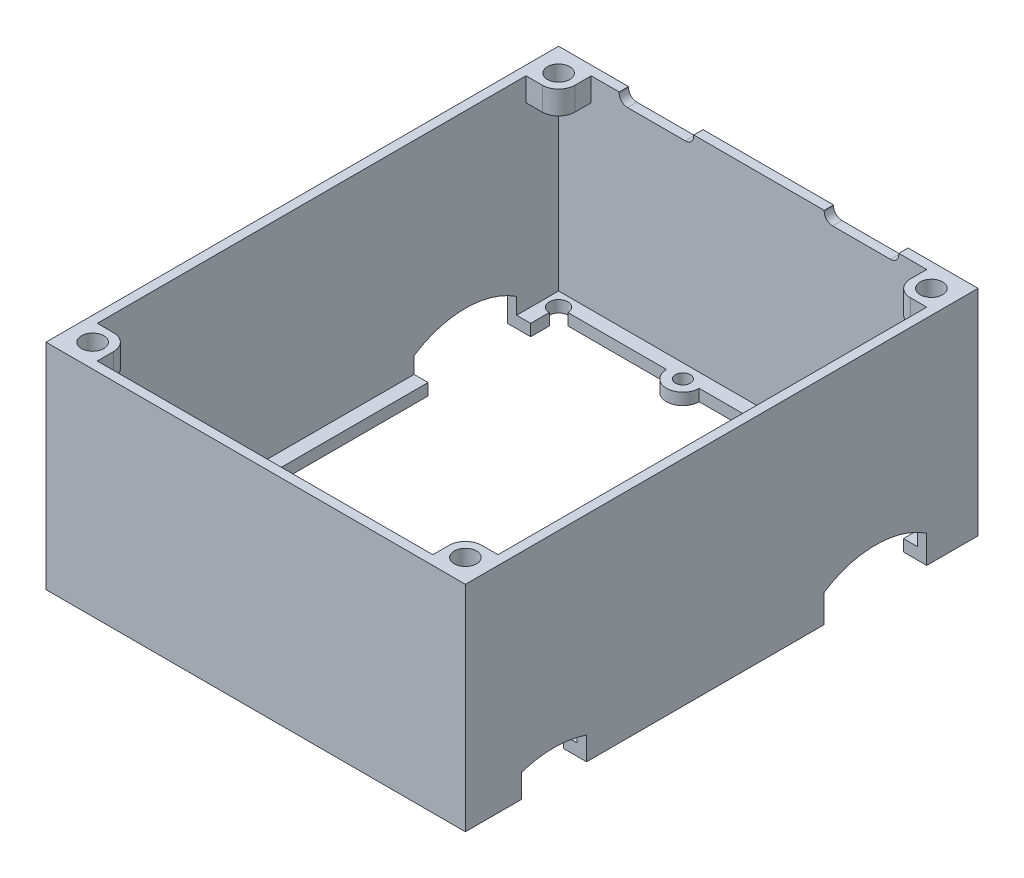
SolidWorks part; units mm, degrees
other "Markup1"
sketch "Sketch7" plane through (-45, 41, -55) normal (0, 1, 0) x (1, 0, 0)
other "DetailItem1"
ref_plane "Front Plane" through (0, 0, 0) normal (0, 0, 1) x (1, 0, 0)
ref_plane "Top Plane" through (0, 0, 0) normal (0, 1, 0) x (1, 0, 0)
ref_plane "Right Plane" through (0, 0, 0) normal (1, 0, 0) x (0, 0, -1)
sketch "Sketch1" plane through (0, 0, 0) normal (0, 1, 0) x (1, 0, 0)
  line L1 (-45, -55) -> (45, -55)
  line L2 (-45, -55) -> (-45, 55)
  line L3 (-45, 55) -> (45, 55)
  line L4 (45, -55) -> (45, 55)
  line L5 (-45, -55) -> (45, 55) construction
  line L6 (-45, 55) -> (45, -55) construction
  point P0 (0, 0)
  dimension "D1" = 90
  dimension "D2" = 110
extrude "Boss-Extrude1" add sketch "Sketch1" along normal blind 2.5
sketch "Sketch2" plane through (0, 2.5, 0) normal (0, 1, 0) x (1, 0, 0)
  line L11 (45, 55) -> (-45, 55) construction
  line L12 (-40, 50) -> (-16.8333, 50)
  line L13 (-40, 50) -> (-40, -50)
  line L14 (-40, -50) -> (-21.5208, -50)
  line L15 (40, 50) -> (40, -50)
  line L16 (-40, 50) -> (40, -50) construction
  line L17 (-40, -50) -> (40, 50) construction
  line L18 (45, -55) -> (45, 55) construction
  line L19 (30.5, 50) -> (40, 50)
  line L20 (-9.8333, 50) -> (23.5, 50)
  line L21 (-14.8126, -50) -> (18.9792, -50)
  line L22 (25.6874, -50) -> (40, -50)
  arc A0 (23.5, 50) -> (30.5, 50) centre (27, 50) ccw
  arc A1 (-14.8126, -50) -> (-21.5208, -50) centre (-18.1667, -51) ccw
  arc A2 (-16.8333, 50) -> (-9.8333, 50) centre (-13.3333, 50) ccw
  arc A3 (25.6874, -50) -> (18.9792, -50) centre (22.3333, -51) ccw
  point P0 (0, 0)
  dimension "D4" = 7
  dimension "D6" = 7
  dimension "D1" = 5
  dimension "D2" = 5
  dimension "D3" = 27
  dimension "D5" = 13.3333
  dimension "D7" = 22.3333
  dimension "D8" = 18.1667
  dimension "D9" = 51
extrude "Cut-Extrude1" cut sketch "Sketch2" against normal through all
sketch "Sketch6" plane through (0, 2.5, 0) normal (0, 1, 0) x (1, 0, 0)
  circle A0 centre (-13.3333, 50) radius 1.6
  circle A1 centre (27, 50) radius 1.6
  circle A2 centre (22.3333, -51) radius 1.6
  circle A3 centre (-18.1667, -51) radius 1.6
  dimension "D1" = 3.2
extrude "Cut-Extrude4" cut sketch "Sketch6" against normal through all
sketch "Sketch3" plane through (0, 2.5, 0) normal (0, 1, 0) x (1, 0, 0)
  line L0 (45, 55) -> (-45, 55) construction
  line L1 (43, -53) -> (-43, -53)
  line L2 (43, -53) -> (43, 53)
  line L3 (43, 53) -> (-43, 53)
  line L4 (-43, -53) -> (-43, 53)
  line L5 (43, -53) -> (-43, 53) construction
  line L6 (43, 53) -> (-43, -53) construction
  line L7 (-45, 55) -> (-45, -55) construction
  point P0 (0, 0)
  line M16 (45, -55) -> (45, 55)
  line M17 (45, 55) -> (-45, 55)
  line M18 (-45, 55) -> (-45, -55)
  line M19 (-45, -55) -> (45, -55)
  dimension "D1" = 2
  dimension "D2" = 2
extrude "Boss-Extrude2" add sketch "Sketch3" along normal blind 43.5 contours L1 L4 L3 L2 M19 M16 M17 M18 region at (0, 2.5, 53.5787)
sketch "Sketch4" plane through (0, 46, 0) normal (0, 1, 0) x (1, 0, 0)
  line L1 (-43, 53) -> (-36, 53)
  line L2 (-43, 53) -> (-43, 46)
  line L3 (-43, 46) -> (-36, 46)
  line L4 (-36, 53) -> (-36, 46)
  dimension "D1" = 7
  dimension "D2" = 7
extrude "Boss-Extrude3" add sketch "Sketch4" against normal blind 5
sketch "Sketch5" plane through (0, 46, 0) normal (0, 1, 0) x (1, 0, 0)
  line L0 (45, 55) -> (-45, 55) construction
  line L1 (-45, 55) -> (-45, -55) construction
  circle A0 centre (-40, 50) radius 2.4
  dimension "D3" = 4.8
  dimension "D1" = 5
  dimension "D2" = 5
extrude "Cut-Extrude3" cut sketch "Sketch5" against normal up to next
mirror "Mirror1" about plane through (0, 0, 0) normal (1, 0, 0) of "Boss-Extrude3", "Cut-Extrude3"
mirror "Mirror2" about plane through (0, 0, 0) normal (0, 0, 1) of "Mirror1"
sketch "Sketch8" plane through (0, 2.5, 0) normal (0, 1, 0) x (1, 0, 0)
  circle A0 centre (-18.1667, -51) radius 3
  circle A1 centre (22.3333, -51) radius 3
  circle A2 centre (22.3333, -51) radius 1.6 construction
  dimension "D1" = 6
extrude "Cut-Extrude5" cut sketch "Sketch8" along normal blind 10
sketch "Sketch9" plane through (-45, 0, 0) normal (-1, 0, 0) x (0, 0, 1)
  line L1 (-44, 6) -> (-44, 0)
  line L2 (-55, 0) -> (55, 0) construction
  line L3 (-44, 0) -> (-22, 0)
  line L4 (-22, 0) -> (-22, 6)
  line L5 (29, 0) -> (43, 0)
  line L6 (29, 0) -> (29, 5)
  line L8 (43, 0) -> (43, 5)
  arc A1 (-44, 6) -> (-22, 6) centre (-33, -10.7033) cw
  arc A2 (29, 5) -> (43, 5) centre (36, -15.8567) cw
  point P0 (-33, 0)
  point P15 (0, 0)
  point P16 (36, 0)
  point P17 (36.3452, -15.9693)
  dimension "D1" = 33
  dimension "D3" = 20
  dimension "D5" = 22
  dimension "D2" = 22
  dimension "D4" = 6
  dimension "D6" = 14
  dimension "D7" = 5
  dimension "D8" = 36
extrude "Cut-Extrude6" cut sketch "Sketch9" against normal through all
sketch "Sketch10" plane through (0, 0, -55) normal (0, 0, -1) x (-1, 0, 0)
  line L0 (0, 24.75) -> (0, -24.75) construction
  line L1 (-45, 46) -> (45, 46) construction
  line L2 (14, 46) -> (30, 46)
  line L3 (14, 46) -> (14, 45.8)
  line L4 (15.8, 44) -> (28.2, 44)
  line L5 (30, 46) -> (30, 45.8)
  line L6 (-30, 46) -> (-30, 45.8)
  line L7 (-15.8, 44) -> (-28.2, 44)
  line L8 (-14, 46) -> (-14, 45.8)
  line L9 (-14, 46) -> (-30, 46)
  arc A0 (28.2, 44) -> (30, 45.8) centre (28.2, 45.8) ccw
  arc A1 (14, 45.8) -> (15.8, 44) centre (15.8, 45.8) ccw
  arc A2 (-14, 45.8) -> (-15.8, 44) centre (-15.8, 45.8) cw
  arc A3 (-28.2, 44) -> (-30, 45.8) centre (-28.2, 45.8) cw
  point P7 (22, 44)
  dimension "D3" = 16
  dimension "D4" = 1.8
  dimension "D1" = 2
  dimension "D2" = 22
extrude "Cut-Extrude7" cut sketch "Sketch10" against normal up to next
sketch "Sketch12" plane through (0, 0, 0) normal (0, 1, 0) x (1, 0, 0)
  circle A0 centre (-40, -50) radius 2
  circle A1 centre (-40, -50) radius 2.4 construction
  circle A2 centre (40, -50) radius 2
  circle A3 centre (-40, 50) radius 2
  circle A4 centre (40, 50) radius 2
  circle A5 centre (-40, 50) radius 2.4 construction
  circle A6 centre (40, 50) radius 2.4 construction
  circle A7 centre (40, -50) radius 2.4 construction
  dimension "D1" = 4
extrude "Cut-Extrude8" cut sketch "Sketch12" along normal blind 5
chamfer "Chamfer1" distance 0.6 angle 60 4 edges at (40, 41, -47.6) (40, 41, 52.4) (-40, 41, 52.4) (-40, 41, -47.6) first distance on face at (40, 46, -47.6) first distance on face at (40, 41, 52.4) first distance on face at (-40, 46, 47.6) first distance on face at (-40, 41, -47.6)
sketch "Sketch11" plane through (0, 46, 0) normal (0, 1, 0) x (1, 0, 0)
  line L1 (-34.7858, 56.1015) -> (-45.2142, 56.1015)
  line L2 (-34.7858, 56.1015) -> (-34.7858, 43.8985)
  line L3 (-34.7858, 43.8985) -> (-45.2142, 43.8985)
  line L4 (-45.2142, 56.1015) -> (-45.2142, 43.8985)
  line L5 (-34.7858, 56.1015) -> (-45.2142, 43.8985) construction
  line L6 (-34.7858, 43.8985) -> (-45.2142, 56.1015) construction
  point P0 (-40, 50)
extrude "Boss-Extrude4" [suppressed] add sketch "Sketch11" against normal blind 5 separate body
other "Intersect1" [suppressed]
fillet "Fillet1" radius 3.5 4 edges at (36, 43.5, 46) (36, 43.5, -46) (-36, 43.5, -46) (-36, 43.5, 46)
equation "\"D4@Sketch2\"=\"D6@Sketch2\""
